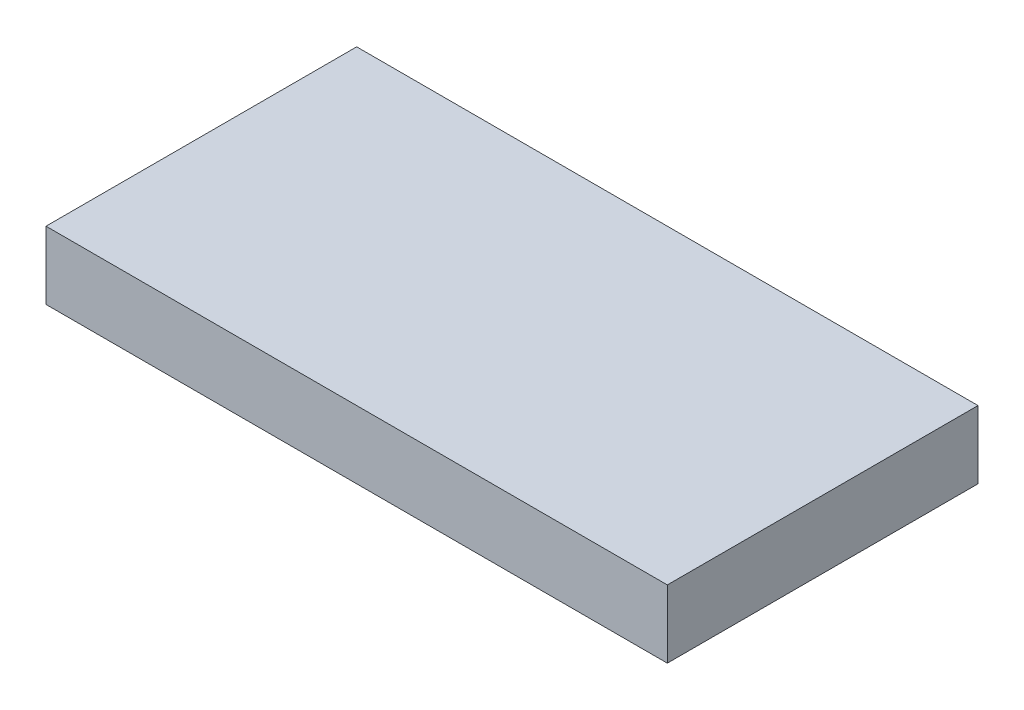
SolidWorks part; units mm, degrees
ref_plane "Plan de face" through (0, 0, 0) normal (0, 0, 1) x (1, 0, 0)
ref_plane "Plan de dessus" through (0, 0, 0) normal (0, 1, 0) x (1, 0, 0)
ref_plane "Plan de droite" through (0, 0, 0) normal (1, 0, 0) x (0, 0, -1)
sketch "Esquisse1" plane through (0, 0, 0) normal (0, 1, 0) x (1, 0, 0)
  line L1 (0, 0) -> (110, 0)
  line L2 (0, 0) -> (0, 55)
  line L3 (0, 55) -> (110, 55)
  line L4 (110, 0) -> (110, 55)
  dimension "D1" = 110
  dimension "D2" = 55
extrude "Boss.-Extru.1" add sketch "Esquisse1" along normal blind 12
